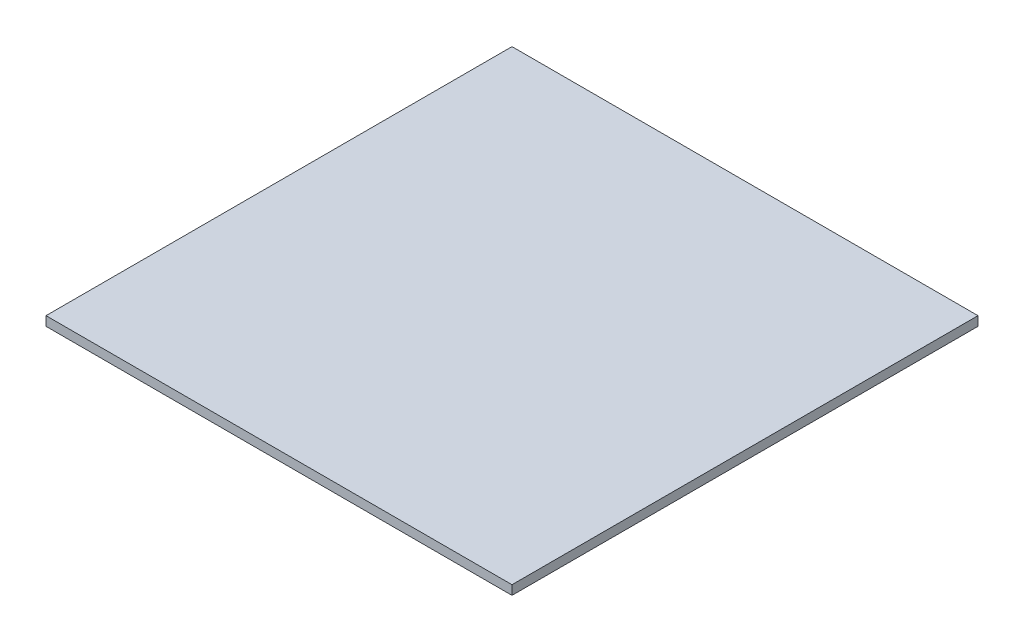
SolidWorks part; units mm, degrees
material "6061 Alloy"
ref_plane "Front" through (0, 0, 0) normal (0, 0, 1) x (1, 0, 0)
ref_plane "Top" through (0, 0, 0) normal (0, 1, 0) x (1, 0, 0)
ref_plane "Right" through (0, 0, 0) normal (1, 0, 0) x (0, 0, -1)
sketch "Sketch1" plane through (0, 0, 0) normal (0, 1, 0) x (1, 0, 0)
  line L1 (0, 0) -> (-108.712, 0)
  line L2 (0, 0) -> (0, 108.712)
  line L3 (0, 108.712) -> (-108.712, 108.712)
  line L4 (-108.712, 0) -> (-108.712, 108.712)
  dimension "D1" = 108.712
  dimension "D2" = 108.712
extrude "Main Plate" add sketch "Sketch1" along normal blind 6.35
sketch "Sketch2" plane through (0, 6.35, 0) normal (0, 1, 0) x (1, 0, 0)
  line L0 (-108.712, 0) -> (0, 0) construction
  line L1 (-118.237, 118.237) -> (9.525, 118.237)
  line L2 (-118.237, 118.237) -> (-118.237, -9.525)
  line L3 (-118.237, -9.525) -> (9.525, -9.525)
  line L4 (9.525, 118.237) -> (9.525, -9.525)
  line L5 (0, 108.712) -> (-108.712, 108.712) construction
  line L6 (-108.712, 108.712) -> (-108.712, 0) construction
  line L7 (0, 0) -> (0, 108.712) construction
  dimension "D1" = 9.525
  dimension "D2" = 9.525
  dimension "D3" = 9.525
  dimension "D4" = 9.525
extrude "Boss-Extrude2" add sketch "Sketch2" along normal blind 2.54
